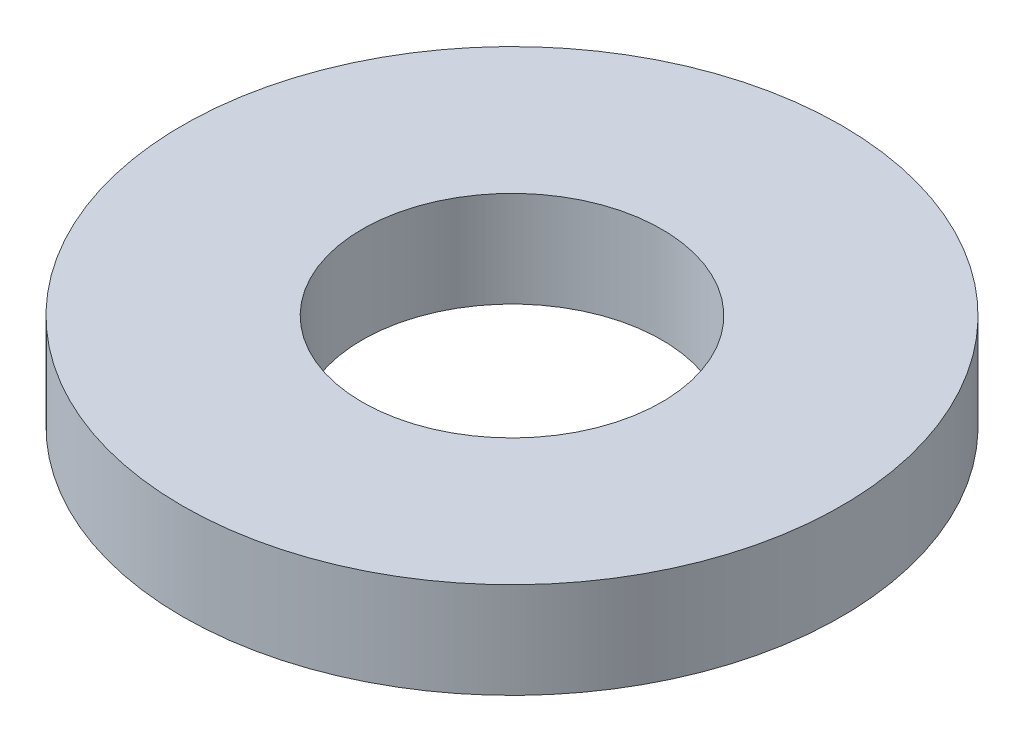
SolidWorks part; units mm, degrees
ref_plane "Front Plane" through (0, 0, 0) normal (0, 0, 1) x (1, 0, 0)
ref_plane "Top Plane" through (0, 0, 0) normal (0, 1, 0) x (1, 0, 0)
ref_plane "Right Plane" through (0, 0, 0) normal (1, 0, 0) x (0, 0, -1)
sketch "Sketch1" plane through (0, 0, 0) normal (0, 1, 0) x (1, 0, 0)
  circle A0 centre (0, 0) radius 55
  dimension "FLANGE_OD" = 110
extrude "Boss-Extrude1" add sketch "Sketch1" along normal blind 16
sketch "Sketch2" plane through (0, 0, 0) normal (0, 1, 0) x (1, 0, 0)
  circle A0 centre (0, 0) radius 25
  dimension "BORE_D" = 50
extrude "Cut-Extrude1" cut sketch "Sketch2" along normal through all
sketch "Sketch3" plane through (0, 16, 0) normal (0, 1, 0) x (1, 0, 0)
  circle A0 centre (0, 0) radius 18.8799 construction
  circle A1 centre (-18.8799, 0) radius 2.9332
  dimension "BOLT_D" = 5.8663
  dimension "BOLT_PCD" = 37.7598
extrude "Cut-Extrude2" cut sketch "Sketch3" against normal blind 14.5726 rebuild error yes
pattern_circular "CirPattern1" count 8 over 360 rebuild error yes
